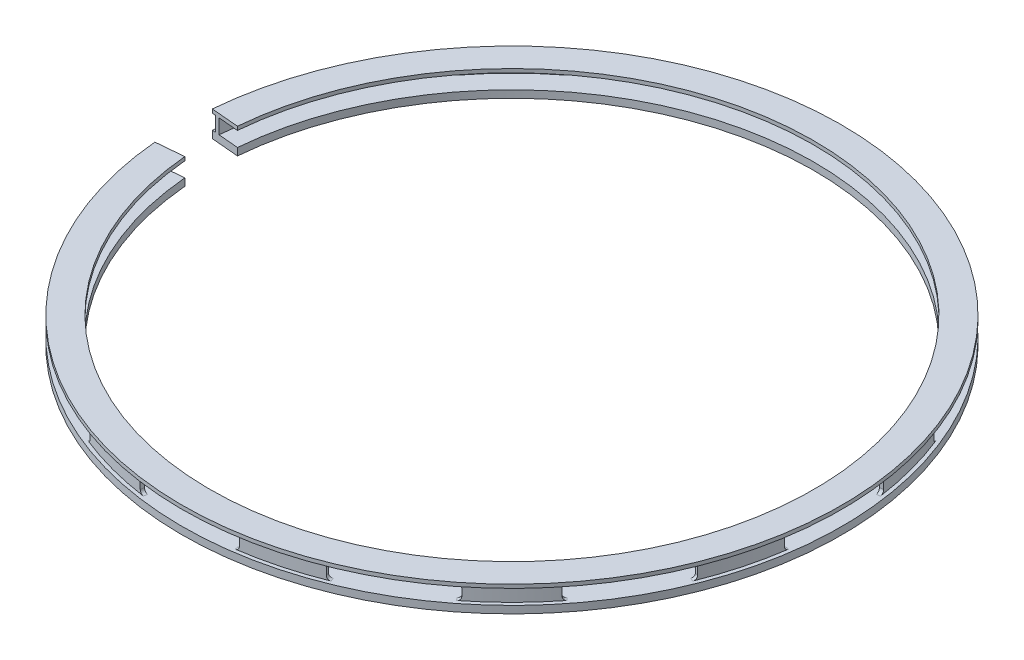
SolidWorks part; units mm, degrees
ref_plane "Front Plane" through (0, 0, 0) normal (0, 0, 1) x (1, 0, 0)
ref_plane "Top Plane" through (0, 0, 0) normal (0, 1, 0) x (1, 0, 0)
ref_plane "Right Plane" through (0, 0, 0) normal (1, 0, 0) x (0, 0, -1)
sketch "Sketch1" plane through (0, 0, 0) normal (0, 0, 1) x (1, 0, 0)
  line L0 (0, 0) -> (0, 7.7273) construction
  line L1 (41, 0) -> (44.75, 0)
  line L2 (44.75, 0) -> (44.75, 1)
  line L3 (44.75, 1) -> (44.25, 1)
  line L4 (44.25, 1) -> (44.25, 3)
  line L5 (44.25, 3.5) -> (44.75, 3.5)
  line L6 (44.75, 3.5) -> (44.75, 3)
  line L7 (44.75, 3) -> (44.25, 3)
  line L8 (41, 3) -> (41, 3.5)
  line L9 (41, 3.5) -> (43.75, 3.5)
  line L10 (43.75, 3) -> (43.75, 1)
  line L11 (43.75, 1) -> (41, 1)
  line L12 (41, 1) -> (41, 0)
  line L13 (43.75, 3.5) -> (44.25, 3.5)
  line L14 (43.75, 3) -> (41, 3)
  dimension "D1" = 3.75
  dimension "D2" = 0.5
  dimension "D3" = 1
  dimension "D4" = 3
  dimension "D5" = 2
  dimension "D6" = 0.5
  dimension "D7" = 41
revolve "Revolve2" add sketch "Sketch1" angle 350 mid plane about L0
sketch "Sketch2" plane through (0, 0, 0) normal (0, 0, 1) x (1, 0, 0)
  line L0 (0, 0) -> (0, 21.4417) construction
  line L1 (-44.0816, 3) -> (44.25, 3) construction
  line L2 (44.25, 1) -> (43.25, 1)
  line L3 (44.25, 1) -> (44.25, 3)
  line L4 (44.25, 3) -> (43.25, 3)
  line L5 (43.25, 1) -> (43.25, 3)
  dimension "D1" = 1
revolve "Cut-Revolve1" cut sketch "Sketch2" angle 17.5 mid plane about L0
fillet "Fillet1" radius 0.5 4 edges at (43.4879, 3, 6.6934) (43.4879, 1, 6.6934) (43.4879, 3, -6.6934) (43.4879, 1, -6.6934)
pattern_circular "CirPattern2" count 12 over 360 about axis through (0, 3.5, 0) along (0, -1, 0) skipping 6 of "Fillet1", "Cut-Revolve1"
